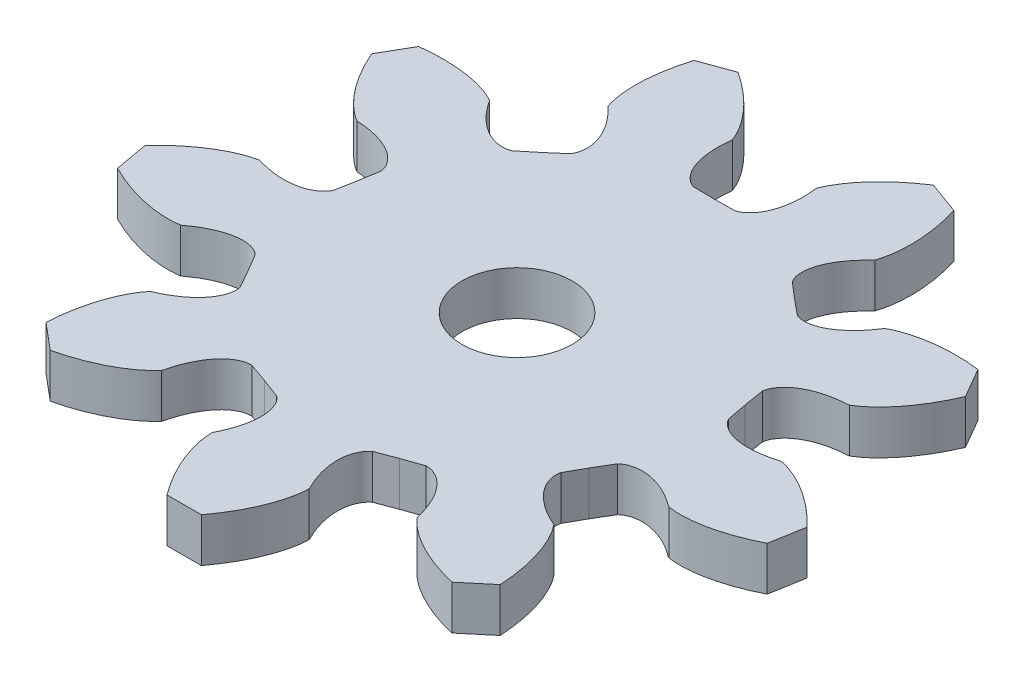
SolidWorks part; units mm, degrees
ref_plane "Plano frontal" through (0, 0, 0) normal (0, 0, 1) x (1, 0, 0)
ref_plane "Plano superior" through (0, 0, 0) normal (0, 1, 0) x (1, 0, 0)
ref_plane "Plano direito" through (0, 0, 0) normal (1, 0, 0) x (0, 0, -1)
sketch "Esboço1" plane through (0, 0, 0) normal (0, 1, 0) x (1, 0, 0)
  line L0 (-25.3837, 16.4538) -> (-26.9413, 13.7561)
  line L1 (-17.2988, 4.9706) -> (-17.6034, 3.104)
  line L2 (-17.6034, 3.104) -> (-17.9556, 1.2457)
  line L3 (-8.8688, 28.9207) -> (-11.796, 27.8553)
  line L4 (-30.0214, -3.712) -> (-29.4805, -6.7798)
  line L5 (-16.4467, -7.3117) -> (-15.4802, -8.9375)
  line L6 (-15.4802, -8.9375) -> (-14.5555, -10.5874)
  line L7 (-10.0566, 14.9272) -> (-11.4898, 13.6931)
  line L8 (-11.4898, 13.6931) -> (-12.9541, 12.4959)
  line L9 (11.796, 27.8553) -> (8.8688, 28.9207)
  line L10 (1.8912, 17.8991) -> (0, 17.875)
  line L11 (0, 17.875) -> (-1.8912, 17.8991)
  line L12 (26.9413, 13.7561) -> (25.3837, 16.4538)
  line L13 (12.9541, 12.4959) -> (11.4898, 13.693)
  line L14 (11.4898, 13.693) -> (10.0566, 14.9272)
  line L15 (29.4805, -6.7798) -> (30.0214, -3.712)
  line L16 (17.9556, 1.2457) -> (17.6034, 3.1039)
  line L17 (17.6034, 3.1039) -> (17.2988, 4.9706)
  line L18 (18.2254, -24.1433) -> (20.6117, -22.1409)
  line L19 (14.5555, -10.5874) -> (15.4802, -8.9375)
  line L20 (15.4802, -8.9375) -> (16.4467, -7.3117)
  line L21 (-1.5575, -30.2099) -> (1.5575, -30.2099)
  line L22 (4.3447, -17.4665) -> (6.1136, -16.797)
  line L23 (6.1136, -16.797) -> (7.899, -16.1728)
  line L24 (-20.6117, -22.1409) -> (-18.2254, -24.1433)
  line L25 (-7.899, -16.1728) -> (-6.1136, -16.797)
  line L26 (-6.1136, -16.797) -> (-4.3447, -17.4665)
  circle A2 centre (0, 0) radius 5
  spline S0 degree 3 number of poles 420 (-17.9564, 15.4545) -> (-25.3837, 16.4538)
  spline S1 degree 3 number of poles 364 (-12.9541, 12.4959) -> (-17.9564, 15.4545)
  spline S2 degree 3 number of poles 364 (-22.3622, 7.8235) -> (-17.2988, 4.9706)
  spline S3 degree 3 number of poles 420 (-26.9413, 13.7561) -> (-22.3622, 7.8235)
  spline S4 degree 3 number of poles 364 (-17.9556, 1.2457) -> (-23.6894, 0.2967)
  spline S5 degree 3 number of poles 420 (-23.6894, 0.2967) -> (-30.0214, -3.712)
  spline S6 degree 3 number of poles 420 (-29.4805, -6.7798) -> (-22.1593, -8.381)
  spline S7 degree 3 number of poles 364 (-22.1593, -8.381) -> (-16.4467, -7.3117)
  spline S8 degree 3 number of poles 420 (-3.8215, 23.381) -> (-8.8688, 28.9207)
  spline S9 degree 3 number of poles 364 (-1.8912, 17.8991) -> (-3.8215, 23.381)
  spline S10 degree 3 number of poles 364 (-12.1016, 20.3673) -> (-10.0566, 14.9272)
  spline S11 degree 3 number of poles 420 (-11.796, 27.8553) -> (-12.1016, 20.3673)
  spline S12 degree 3 number of poles 420 (12.1016, 20.3673) -> (11.796, 27.8553)
  spline S13 degree 3 number of poles 364 (10.0566, 14.9272) -> (12.1016, 20.3673)
  spline S14 degree 3 number of poles 364 (3.8215, 23.381) -> (1.8912, 17.8991)
  spline S15 degree 3 number of poles 420 (8.8688, 28.9207) -> (3.8215, 23.381)
  spline S16 degree 3 number of poles 420 (22.3622, 7.8235) -> (26.9413, 13.7561)
  spline S17 degree 3 number of poles 364 (17.2988, 4.9706) -> (22.3622, 7.8235)
  spline S18 degree 3 number of poles 364 (17.9564, 15.4545) -> (12.9541, 12.4959)
  spline S19 degree 3 number of poles 420 (25.3837, 16.4538) -> (17.9564, 15.4545)
  spline S20 degree 3 number of poles 420 (22.1593, -8.381) -> (29.4805, -6.7798)
  spline S21 degree 3 number of poles 364 (16.4467, -7.3117) -> (22.1593, -8.381)
  spline S22 degree 3 number of poles 364 (23.6894, 0.2967) -> (17.9556, 1.2457)
  spline S23 degree 3 number of poles 420 (30.0214, -3.712) -> (23.6894, 0.2967)
  spline S24 degree 3 number of poles 420 (11.5878, -20.6639) -> (18.2254, -24.1433)
  spline S25 degree 3 number of poles 364 (7.899, -16.1728) -> (11.5878, -20.6639)
  spline S26 degree 3 number of poles 364 (18.3378, -15) -> (14.5555, -10.5874)
  spline S27 degree 3 number of poles 420 (20.6117, -22.1409) -> (18.3378, -15)
  spline S28 degree 3 number of poles 420 (-4.4058, -23.278) -> (-1.5575, -30.2099)
  spline S29 degree 3 number of poles 364 (-4.3447, -17.4665) -> (-4.4058, -23.278)
  spline S30 degree 3 number of poles 364 (4.4058, -23.278) -> (4.3447, -17.4665)
  spline S31 degree 3 number of poles 420 (1.5575, -30.2099) -> (4.4058, -23.278)
  spline S32 degree 3 number of poles 420 (-18.3378, -15) -> (-20.6117, -22.1409)
  spline S33 degree 3 number of poles 364 (-14.5555, -10.5874) -> (-18.3378, -15)
  spline S34 degree 3 number of poles 364 (-11.5878, -20.6639) -> (-7.899, -16.1728)
  spline S35 degree 3 number of poles 420 (-18.2254, -24.1433) -> (-11.5878, -20.6639)
  point P76 (0, 0)
  dimension "D1" = 9
extrude "Ressalto-extrusão1" add sketch "Esboço1" along normal blind 4
